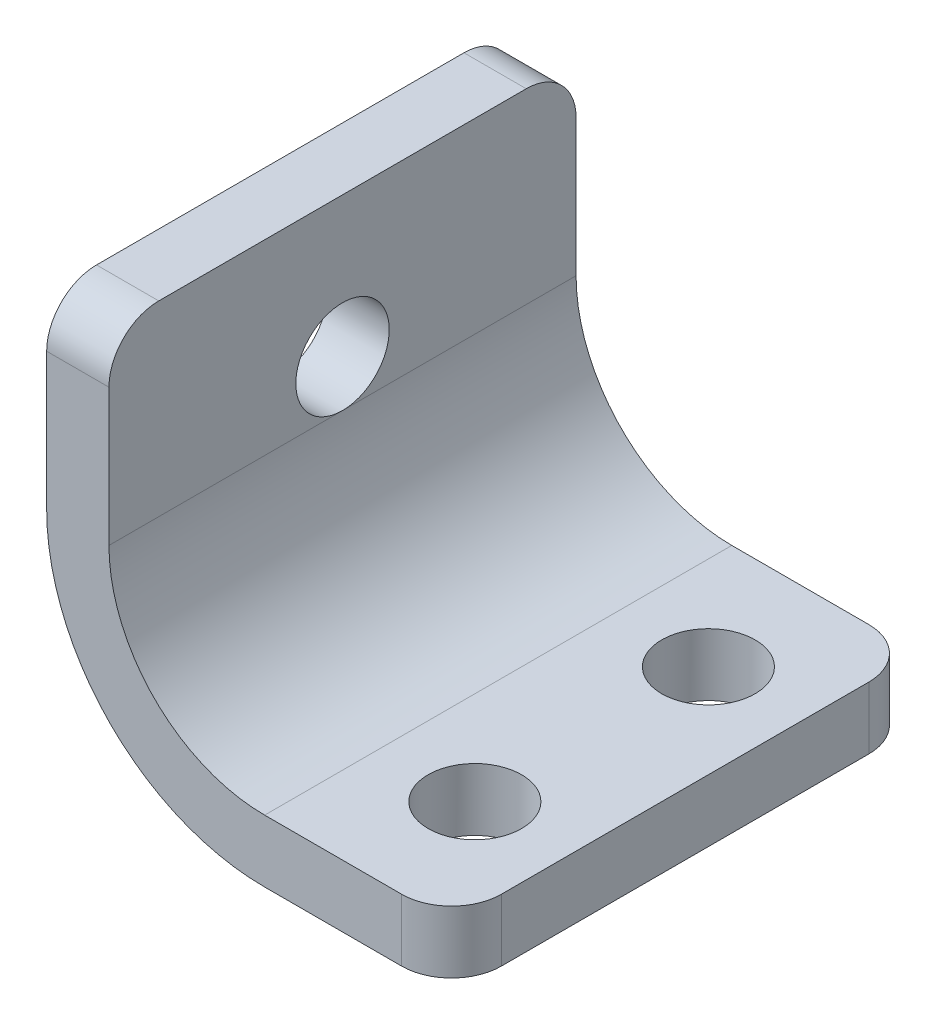
SolidWorks part; units mm, degrees
material "6061 Alloy"
ref_plane "Front Plane" through (0, 0, 0) normal (0, 0, 1) x (1, 0, 0)
ref_plane "Top Plane" through (0, 0, 0) normal (0, 1, 0) x (1, 0, 0)
ref_plane "Right Plane" through (0, 0, 0) normal (1, 0, 0) x (0, 0, -1)
sketch "Sketch1" plane through (0, 0, 0) normal (0, 0, 1) x (1, 0, 0)
  line L0 (0, 22.5158) -> (0, 12.9908)
  line L1 (7.9375, 5.0533) -> (17.4625, 5.0533)
  line L2 (-3.175, 22.5158) -> (-3.175, 12.9908)
  line L3 (7.9375, 1.8783) -> (17.4625, 1.8783)
  line L4 (-3.175, 22.5158) -> (0, 22.5158)
  line L5 (17.4625, 5.0533) -> (17.4625, 1.8783)
  arc A0 (7.9375, 5.0533) -> (0, 12.9908) centre (7.9375, 12.9908) cw
  arc A1 (7.9375, 1.8783) -> (-3.175, 12.9908) centre (7.9375, 12.9908) cw
  dimension "D1" = 7.9375
  dimension "D2" = 9.525
  dimension "D3" = 9.525
  dimension "D4" = 3.175
extrude "Boss-Extrude1" add sketch "Sketch1" along normal blind 23.8125
fillet "Fillet1" radius 2.54 4 edges at (17.4625, 3.4658, 23.8125) (17.4625, 3.4658, 0) (-1.5875, 22.5158, 23.8125) (-1.5875, 22.5158, 0)
sketch "Sketch3" plane through (0, 5.0533, 0) normal (0, 1, 0) x (1, 0, 0)
  line L0 (12.7, -11.9062) -> (12.7, 0) construction
  line L1 (14.9225, -23.8125) -> (7.9375, -23.8125) construction
  line L2 (14.9225, 0) -> (7.9375, 0) construction
  line L3 (17.4625, -11.9062) -> (7.9375, -11.9062) construction
  line L4 (17.4625, -21.2725) -> (17.4625, -2.54) construction
  line L5 (7.9375, -23.8125) -> (7.9375, 0) construction
  line L6 (12.7, -11.9062) -> (12.7, -23.8125) construction
  circle A0 centre (12.7, -17.8594) radius 2.3813
  circle A1 centre (12.7, -5.9531) radius 2.3813
  point P19 (12.7, -5.9531)
  point P21 (12.7, -17.8594)
  dimension "D3" = 4.7625
  dimension "D4" = 4.7625
extrude "Cut-Extrude2" cut sketch "Sketch3" against normal up to next contours A0 | A0 | A1 | A1 region at (12.7, 5.0533, 17.8594) region at (12.7, 5.0533, 5.9531)
sketch "Sketch5" plane through (0, 0, 0) normal (1, 0, 0) x (0, 0, -1)
  line L1 (-11.9062, 12.9908) -> (-11.9062, 15.372) construction
  line L4 (-2.54, 22.5158) -> (-21.2725, 22.5158)
  line L5 (-23.8125, 19.9758) -> (-23.8125, 12.9908)
  line L6 (-23.8125, 12.9908) -> (0, 12.9908)
  line L7 (0, 12.9908) -> (0, 19.9758)
  line L8 (-2.54, 22.5158) -> (-21.2725, 22.5158)
  line L9 (-23.8125, 19.9758) -> (-23.8125, 12.9908)
  line L10 (-23.8125, 12.9908) -> (0, 12.9908)
  line L11 (0, 12.9908) -> (0, 19.9758)
  circle A1 centre (-11.9062, 15.372) radius 2.3813
  arc A2 (-21.2725, 22.5158) -> (-23.8125, 19.9758) centre (-21.2725, 19.9758) ccw
  arc A3 (0, 19.9758) -> (-2.54, 22.5158) centre (-2.54, 19.9758) ccw
  arc A4 (-21.2725, 22.5158) -> (-23.8125, 19.9758) centre (-21.2725, 19.9758) ccw
  arc A5 (0, 19.9758) -> (-2.54, 22.5158) centre (-2.54, 19.9758) ccw
  dimension "D2" = 4.7625
  dimension "D1" = 0
extrude "Cut-Extrude3" cut sketch "Sketch5" against normal up to next contours L1 A1 | A1 L1 region at (0, 15.372, 11.9062)
sketch "Sketch4" plane through (0, 1.8783, 0) normal (0, -1, 0) x (1, 0, 0)
  line L0 (7.9375, 11.9062) -> (17.4625, 11.9062)
  line L1 (7.9375, 23.8125) -> (7.9375, 0) construction
  line L2 (17.4625, 21.2725) -> (17.4625, 2.54) construction
